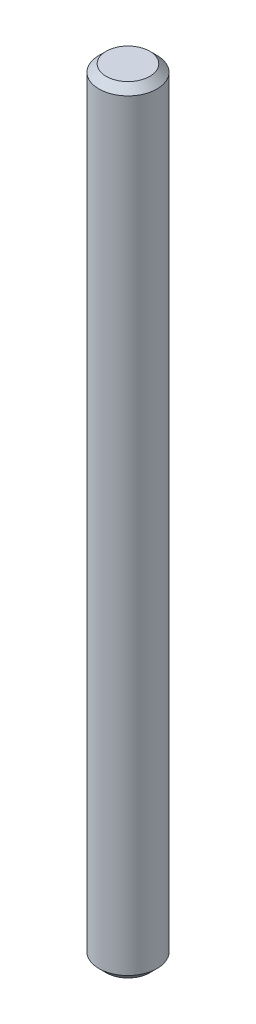
SolidWorks part; units mm, degrees
ref_plane "Front Plane" through (0, 0, 0) normal (0, 0, 1) x (1, 0, 0)
ref_plane "Top Plane" through (0, 0, 0) normal (0, 1, 0) x (1, 0, 0)
ref_plane "Right Plane" through (0, 0, 0) normal (1, 0, 0) x (0, 0, -1)
ref_plane "Plane1" through (0, 0, 0) normal (0, 0, 1) x (1, 0, 0)
sketch "Sketch1" plane through (0, 0, 0) normal (0, 0, 1) x (1, 0, 0)
  line L0 (0, 26.7) -> (1.5, 26.7)
  line L1 (1.5, 26.7) -> (2, 26.2)
  line L2 (2, 26.2) -> (2, -26.2)
  line L3 (2, -26.2) -> (1.5, -26.7)
  line L4 (1.5, -26.7) -> (0, -26.7)
  line L5 (0, -26.7) -> (0, 26.7)
  line L6 (0, -26.7) -> (0, 26.7) construction
revolve "Revolve1" add sketch "Sketch1" angle 360 about L6 reverse direction yes
